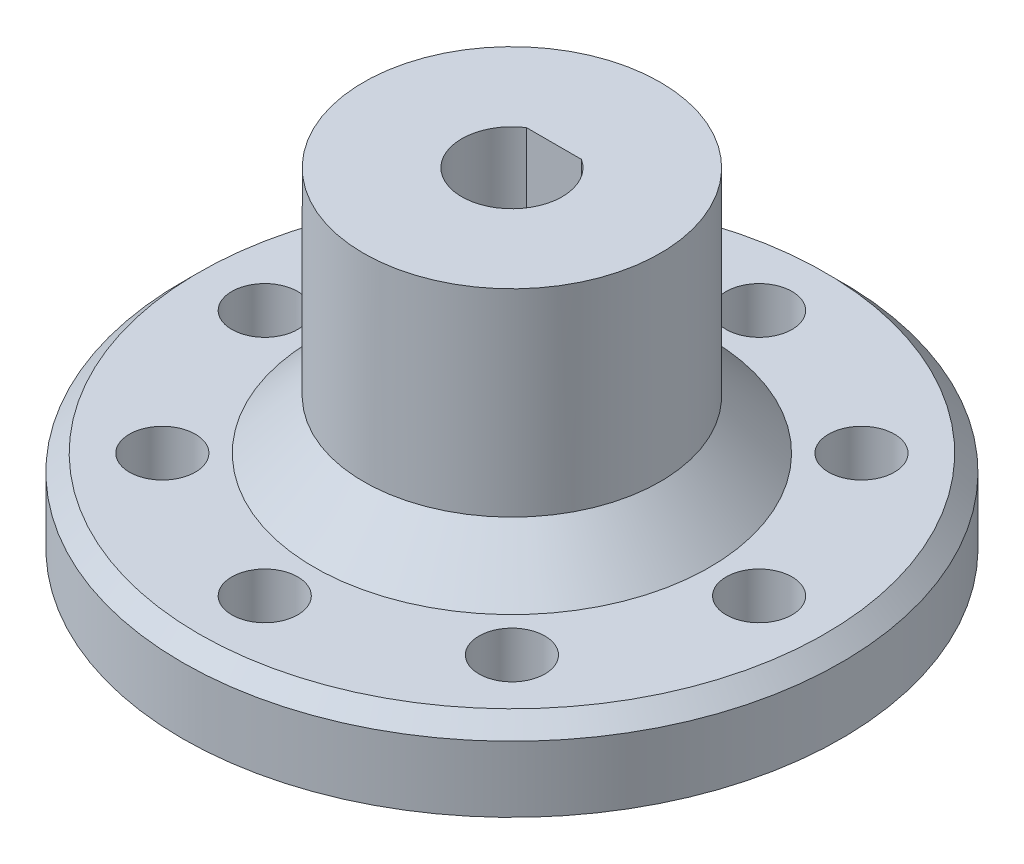
SolidWorks part; units mm, degrees
material "PLA"
ref_plane "Front" through (0, 0, 0) normal (0, 0, 1) x (1, 0, 0)
ref_plane "Top" through (0, 0, 0) normal (0, 1, 0) x (1, 0, 0)
ref_plane "Right" through (0, 0, 0) normal (1, 0, 0) x (0, 0, -1)
sketch "Sketch1" plane through (0, 0, 0) normal (0, 1, 0) x (1, 0, 0)
  circle A0 centre (0, 0) radius 20
  dimension "D1" = 40
extrude "Boss-Extrude1" add sketch "Sketch1" along normal blind 5
sketch "Sketch2" plane through (0, 5, 0) normal (0, 1, 0) x (1, 0, 0)
  circle A0 centre (0, 15) radius 2
  circle A1 centre (10.6066, 10.6066) radius 2
  circle A2 centre (15, 0) radius 2
  circle A3 centre (10.6066, -10.6066) radius 2
  circle A4 centre (0, -15) radius 2
  circle A5 centre (-10.6066, -10.6066) radius 2
  circle A6 centre (-15, 0) radius 2
  circle A7 centre (-10.6066, 10.6066) radius 2
  point P19 (0, 0)
  dimension "D1" = 4
  dimension "D2" = 15
  dimension "D3" = 8
extrude "Cut-Extrude1" cut sketch "Sketch2" against normal through all
sketch "Sketch3" plane through (0, 5, 0) normal (0, 1, 0) x (1, 0, 0)
  circle A0 centre (0, 0) radius 9
  dimension "D1" = 18
extrude "Boss-Extrude2" add sketch "Sketch3" along normal blind 15
sketch "Sketch4" plane through (0, 20, 0) normal (0, 1, 0) x (1, 0, 0)
  line L0 (-1.6733, 2.55) -> (1.6733, 2.55)
  line L1 (0, 0) -> (0, -3.05) construction
  circle A0 centre (0, 0) radius 3.05
  dimension "D1" = 6.1
  dimension "D2" = 5.6
extrude "Cut-Extrude2" cut sketch "Sketch4" against normal through all contours L0 A0 region at (0, 20, 0.1112)
sketch "Sketch5" plane through (0, 20, 0) normal (0, 1, 0) x (1, 0, 0)
  line L1 (-0.5, -9) -> (0.5, -9)
  line L2 (-0.5, -9) -> (-0.5, 4)
  line L3 (-0.5, 4) -> (0.5, 4)
  line L4 (0.5, -9) -> (0.5, 4)
  line L5 (-0.5, -9) -> (0.5, 4) construction
  line L6 (-0.5, 4) -> (0.5, -9) construction
  circle A0 centre (0, 0) radius 9 construction
  point P0 (0, -2.5)
  dimension "D1" = 1
  dimension "D2" = 4
extrude "Cut-Extrude3" [suppressed] cut sketch "Sketch5" against normal blind 12
ref_plane "Plane1" [suppressed] through (9, 0, 0) normal (1, 0, 0) x (0, 0, -1)
sketch "Sketch7" [suppressed] plane through (9, 0, 0) normal (1, 0, 0) x (0, 0, -1)
  line L0 (9, 5) -> (9, 20) construction
  line L1 (9, 8) -> (-8.9861, 8)
  line L2 (9, 8) -> (9, 9)
  line L3 (9, 9) -> (-8.9861, 9)
  line L4 (-8.9861, 8) -> (-8.9861, 9)
  line L5 (-8.9861, 20) -> (-8.9861, 8) construction
  line L6 (-8.9861, 8) -> (-9, 8) construction
  dimension "D1" = 1
extrude "Cut-Extrude4" [suppressed] cut sketch "Sketch7" against normal up to surface (9.5 mm away)
sketch "Sketch8" [suppressed] plane through (9, 0, 0) normal (1, 0, 0) x (0, 0, -1)
  line L0 (-8.9861, 20) -> (-8.9861, 9) construction
  line L1 (-5.9861, 17.5) -> (-8.9861, 17.5)
  line L2 (-8.9861, 17.5) -> (-8.9861, 11.5)
  line L3 (-8.9861, 11.5) -> (-5.9861, 11.5)
  line L4 (9, 9) -> (9, 20) construction
  line L5 (9, 14.5) -> (-17.854, 14.5) construction
  circle A0 centre (-5.9861, 14.5) radius 3
  dimension "D1" = 6
extrude "Cut-Extrude5" [suppressed] cut sketch "Sketch8" against normal blind 6 contours A0 | A0 L1 L2 | A0 L2 L3
mirror "Mirror1" [suppressed] about plane through (0, 0, 0) normal (1, 0, 0)
sketch "Sketch9" [suppressed] plane through (3, 0, 0) normal (1, 0, 0) x (0, 0, -1)
  circle A0 centre (-5.9861, 14.5) radius 2
  arc A1 (-5.9861, 11.5) -> (-5.9861, 17.5) centre (-5.9861, 14.5) ccw construction
  dimension "D1" = 4
extrude "Cut-Extrude6" [suppressed] cut sketch "Sketch9" against normal through all
chamfer "Chamfer3" distance 3 distance2 3 1 edges at (0, 5, 9)
chamfer "Chamfer4" distance 1 angle 45 1 edges at (0, 5, 20)
ref_plane "Plane2" through (0, 0, -9) normal (0, 0, -1) x (-1, 0, 0)
sketch "Sketch10" plane through (0, 0, -9) normal (0, 0, -1) x (-1, 0, 0)
  line L0 (0, 0) -> (0, 26.0695) construction
  line L1 (2.4249, 18.2) -> (-2.4249, 18.2)
  line L2 (-2.4249, 18.2) -> (-4.8497, 14)
  line L3 (-4.8497, 14) -> (-2.4249, 9.8)
  line L4 (-2.4249, 9.8) -> (2.4249, 9.8)
  line L5 (2.4249, 9.8) -> (4.8497, 14)
  line L6 (4.8497, 14) -> (2.4249, 18.2)
  line L7 (-20, 0) -> (20, 0) construction
  line L8 (3.05, 20) -> (-3.05, 20) construction
  circle A0 centre (0, 14) radius 4.2 construction
  circle A1 centre (0, 14) radius 1.75
  dimension "D1" = 8.4
  dimension "D3" = 3.5
  dimension "D2" = 6
extrude "Cut-Extrude7" cut sketch "Sketch10" against normal blind 3.5 contours A1 | L5 L6 L1 L2 L3 L4 A1 | L1 L2 L3 L4 L5 L6 region at (-3.5262, 16.0358, -9) region at (0, 14, -9)
extrude "Cut-Extrude8" cut sketch "Sketch10<3>" against normal up to next contours A1 region at (0, 14, -9)
sketch "Sketch10<3>" plane through (0, 0, -9) normal (0, 0, -1) x (-1, 0, 0) same geometry as "Sketch10"
